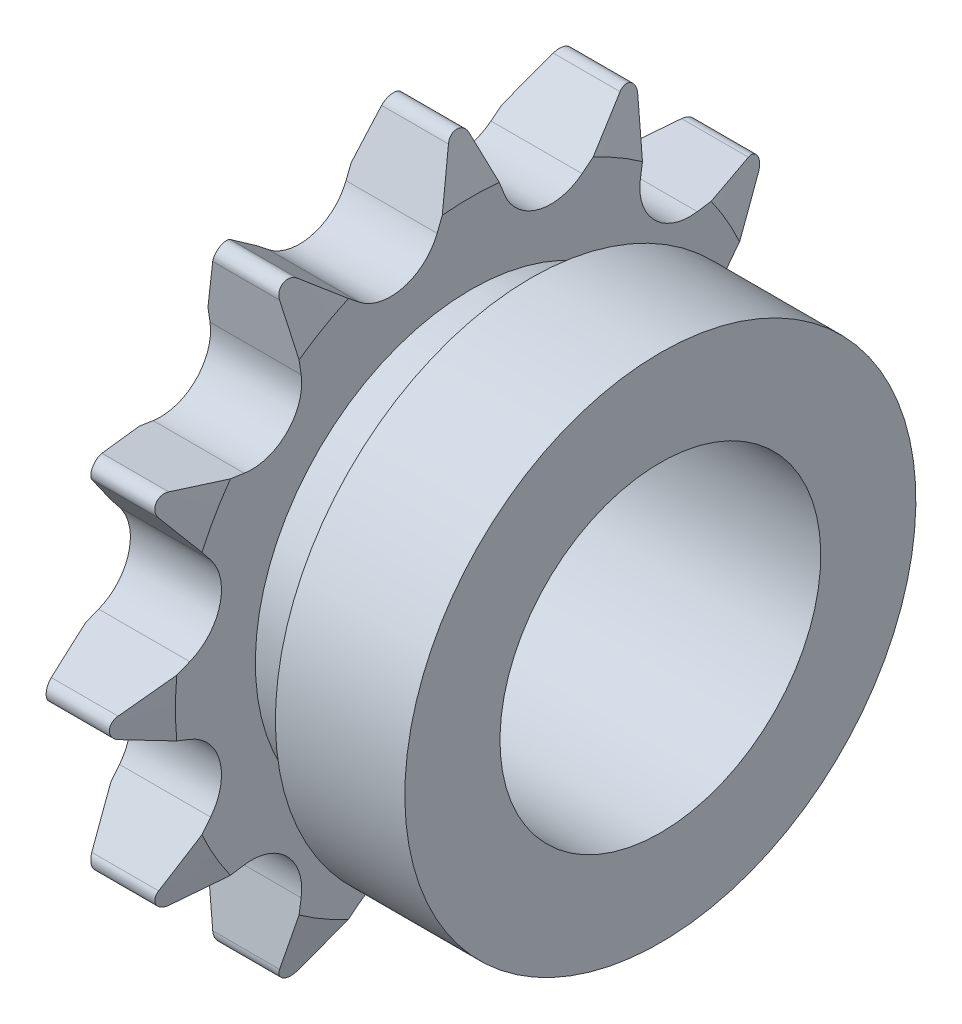
SolidWorks part; units mm, degrees
material "1144"
ref_plane "Front Plane" through (0, 0, 0) normal (0, 0, 1) x (1, 0, 0)
ref_plane "Top Plane" through (0, 0, 0) normal (0, 1, 0) x (1, 0, 0)
ref_plane "Right Plane" through (0, 0, 0) normal (1, 0, 0) x (0, 0, -1)
ref_axis "Axis1" through (-63.0158, 0, 0) along (1, 0, 0)
sketch "Sketch1" plane through (0, 0, 0) normal (0, 0, 1) x (1, 0, 0)
  line L0 (3.6068, 17.0561) -> (3.6068, 0) construction
  line L1 (22.225, 0) -> (22.225, 20.2311)
  line L3 (7.2136, 17.0561) -> (0, 17.0561)
  line L7 (0, 27.5082) -> (0, 30.0482) construction
  line L8 (0, 27.5082) -> (7.2136, 27.5082)
  line L9 (22.225, 0) -> (0, 0)
  line L10 (0, 0) -> (-84.1773, 0) construction
  line L11 (0, 17.0561) -> (0, 27.5082) construction
  line L12 (7.2136, 27.5082) -> (73.2462, 27.5082) construction
  line L13 (22.225, 0) -> (22.225, -20.2311) construction
  line L14 (3.6068, 0) -> (3.6068, -17.0561)
  line L15 (-15.4432, -17.0561) -> (22.6568, -17.0561)
  point P11 (0, 30.0482)
  dimension "D1" = 2.54
  dimension "hub_dia" = 40.4622
  dimension "width_teetth" = 7.2136
  dimension "D2" = 38.1
  dimension "length_thru" = 22.225
  dimension "OD" = 55.0164
  dimension "length_over_teeth" = 7.2136
  dimension "recess_hub_diam" = 34.1122
  dimension "hub_type" = 22.225
  dimension "projection 1" = 15.0114
  dimension "projection 2" = 0
sketch "Sketch2" plane through (0, 0, 0) normal (1, 0, 0) x (0, 0, -1)
  line L0 (0, 0) -> (0, 27.5082) construction
  line L1 (0, 0) -> (-13.7541, 23.8228) construction
  line L2 (0, 0) -> (-6.3502, 23.6991) construction
  line L3 (-0.8057, 26.9597) -> (-2.6638, 22.246)
  line L4 (-2.6638, 22.246) -> (-6.3502, 23.6991) construction
  line L5 (-0.8217, 27.4959) -> (0, 0) construction
  line L6 (-2.735, 27.3719) -> (0, 0) construction
  line L7 (-6.3502, 23.6991) -> (-2.4074, 24.0931) construction
  arc A1 (0, 27.5082) -> (-13.7541, 23.8228) centre (0, 0) ccw
  circle A2 centre (0, 0) radius 24.5351 construction
  circle A3 centre (-6.3502, 23.6991) radius 3.9624
  arc A4 (0, 27.5082) -> (-0.8057, 26.9597) centre (0, 26.6421) ccw
  dimension "pitch_diam" = 49.0703
  dimension "roller_diam" = 7.9248
  dimension "D1" = 1.712
  dimension "ang_1" = 30
  dimension "OD/2" = 27.5082
sketch "Taper Per Foot" plane through (0, 0, 0) normal (0, 0, 1) x (1, 0, 0)
  line L0 (22.225, 0) -> (22.225, 127)
  line L1 (22.225, 0) -> (22.225, 20.2311) construction
  line L2 (22.225, 127) -> (-282.575, 6.35)
  line L3 (-282.575, 6.35) -> (-282.575, 0)
  line L4 (-282.575, 0) -> (22.225, 0)
  line L5 (-282.575, 0) -> (-285.7823, 0) construction
  line L6 (-282.575, 6.35) -> (22.225, 6.35)
  line L7 (22.225, 6.35) -> (22.225, 127)
  dimension "1 Ft" = 304.8
  dimension "1 in" = 254
  dimension "Small End Diam" = 12.7
  dimension "Large End Diam" = 12.7
ref_plane "Plane1" through (7.2136, 0, 0) normal (1, 0, 0) x (0, 0, -1)
ref_plane "Plane2" through (7.2136, 0, 0) normal (1, 0, 0) x (0, 0, -1)
ref_plane "Plane3" through (0, 17.0561, 0) normal (-1, 0, 0) x (0, 0, 1)
ref_plane "Plane4" through (22.225, 0, 0) normal (1, 0, 0) x (0, 0, -1)
ref_plane "Plane5" through (3.6068, 0, 0) normal (1, 0, 0) x (0, 0, -1)
sketch "Sketch13" plane through (0, 0, 0) normal (0, 0, 1) x (1, 0, 0)
  line L0 (22.225, 0) -> (22.225, 20.2311) construction
  line L1 (0, 0) -> (22.225, 0)
  line L2 (0, 0) -> (0, 27.5082)
  line L3 (0, 27.5082) -> (22.225, 27.5082)
  line L4 (22.225, 0) -> (22.225, 27.5082)
revolve "Revolve1" add sketch "Sketch13" angle 360 about L10
sketch "Sketch6" plane through (0, -16.51, 0) normal (1, 0, 0) x (0, 0, -1)
  line L0 (-0.8057, 43.4697) -> (-2.6638, 38.756) construction
  line L1 (-0.8057, 43.4697) -> (-2.6638, 38.756)
  line L2 (-6.3502, 40.2091) -> (0, 16.51) construction
  line L3 (-12.7821, 40.2607) -> (-8.8161, 37.1075)
  arc A0 (0, 44.0182) -> (-0.8057, 43.4697) centre (0, 43.1521) ccw construction
  arc A1 (0, 44.0182) -> (-0.8057, 43.4697) centre (0, 43.1521) ccw
  arc A2 (-13.7541, 40.3328) -> (-12.7821, 40.2607) centre (-13.3211, 39.5828) cw
  arc A3 (-2.6638, 38.756) -> (-8.8161, 37.1075) centre (-6.3502, 40.2091) cw
  arc A4 (0, 44.0182) -> (-13.7541, 40.3328) centre (0, 16.51) ccw
extrude "Cut-Extrude1" cut sketch "Sketch6" along normal up to vertex (7.2136 mm away) up to point (7.2136, 17.0561, 0)
pattern_circular "CirPattern1" count 12 over 360 about axis through (-63.0158, 0, 0) along (1, 0, 0) of "Cut-Extrude1"
sketch "Sketch15" plane through (0, 0, 0) normal (0, 0, 1) x (1, 0, 0)
  line L1 (134.2136, 20.2311) -> (7.2136, 20.2311)
  line L2 (134.2136, 20.2311) -> (134.2136, 42.7482)
  line L3 (134.2136, 42.7482) -> (7.2136, 42.7482)
  line L4 (7.2136, 20.2311) -> (7.2136, 42.7482)
  line L5 (3.6068, 216.4797) -> (3.6068, 17.0561) construction
  line L6 (-127, 20.2311) -> (0, 20.2311)
  line L7 (0, 20.2311) -> (0, 42.7482)
  line L8 (-127, 42.7482) -> (0, 42.7482)
  line L9 (-127, 20.2311) -> (-127, 42.7482)
  dimension "D1" = 12.7
  dimension "D2" = 127
revolve "hub Cut-Revolve3" cut sketch "Sketch15" angle 360 about L10
sketch "Sketch4" plane through (0, 0, 0) normal (0, 0, 1) x (1, 0, 0)
  line L0 (0, 27.5082) -> (1.1045, 27.5082)
  line L2 (1.1045, 27.5082) -> (0, 23.3861)
  line L4 (0, 23.3861) -> (0, 27.5082)
  line L5 (3.6068, 27.5082) -> (3.6068, 44.9612) construction
  line L6 (7.2136, 27.5082) -> (6.1091, 27.5082)
  line L7 (7.2136, 23.3861) -> (7.2136, 27.5082)
  line L8 (6.1091, 27.5082) -> (7.2136, 23.3861)
  line L9 (0, 0) -> (-52.1231, 0) construction
  line L10 (0, 0) -> (-84.1773, 0) construction
  line L17 (0, 27.5082) -> (7.2136, 27.5082) construction
  dimension "D1" = 15
  dimension "D2" = 4.1221
revolve "Teeth Chamfer" cut sketch "Sketch4" angle 360 about L9
sketch "Sketch16" plane through (0, 0, 0) normal (0, 0, 1) x (1, 0, 0)
  line L1 (7.2136, 20.2311) -> (11.9761, 20.2311)
  line L2 (7.2136, 20.2311) -> (7.2136, 17.0561)
  line L3 (7.2136, 17.0561) -> (11.9761, 17.0561)
  line L4 (11.9761, 20.2311) -> (11.9761, 17.0561)
  line L5 (11.9761, 20.2311) -> (22.225, 20.2311) construction
  dimension "recess_width" = 4.7625
  dimension "recess_height" = 3.175
revolve "Recess" cut sketch "Sketch16" angle 360 about L10
sketch "Sketch32" plane through (22.225, 0, 0) normal (1, 0, 0) x (0, 0, -1)
  circle A1 centre (0, 0) radius 20.2311
  circle A2 centre (0, 0) radius 20.2311
  dimension "D1" = 0
extrude "Collar Reduction" [suppressed] cut sketch "Sketch32" against normal offset from surface (1.822 mm away) 20.403
sketch "Sketch34" plane through (0, 0, 0) normal (1, 0, 0) x (0, 0, -1)
  line L0 (0, 0) -> (0, 19.6609) construction
  circle A0 centre (0, 0) radius 12.7
  arc A1 (-3.175, 12.2967) -> (3.175, 12.2967) centre (0, 0) cw
  point P3 (0, 0)
  point P5 (0, 0)
  dimension "D1" = 25.4
extrude "Cut-Extrude3" cut sketch "Sketch34" along normal through all contours A0 A1 region at (0, 0, 0)
ref_plane "Sprocket Teeth Center" through (3.6068, 0, 0) normal (-1, 0, 0) x (0, 0, 1)
sketch "Sketch35" plane through (3.6068, 0, 0) normal (-1, 0, 0) x (0, 0, 1)
  circle A0 centre (0, 0) radius 24.5351 construction
  circle A1 centre (0, 0) radius 24.5351 construction
